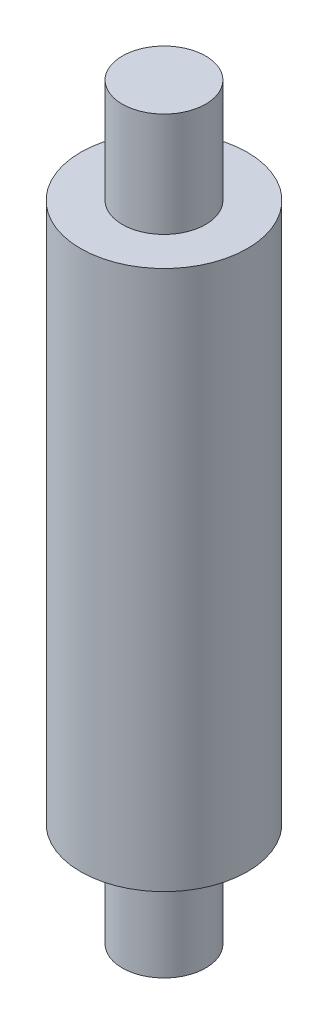
SolidWorks part; units mm, degrees
material "Plain Carbon Steel"
ref_plane "Front Plane" through (0, 0, 0) normal (0, 0, 1) x (1, 0, 0)
ref_plane "Top Plane" through (0, 0, 0) normal (0, 1, 0) x (1, 0, 0)
ref_plane "Right Plane" through (0, 0, 0) normal (1, 0, 0) x (0, 0, -1)
sketch "Sketch1" plane through (0, 0, 0) normal (0, 0, 1) x (1, 0, 0)
  line L0 (0, 30.988) -> (3.4544, 30.988)
  line L1 (3.4544, 30.988) -> (3.4544, 0)
  line L2 (3.4544, 0) -> (0, 0)
  line L3 (0, 0) -> (0, 30.988)
  line L4 (0, 0) -> (0, 30.988) construction
revolve "Revolve1" add sketch "Sketch1" angle 360 about L4 reverse direction yes
sketch "Sketch2" plane through (0, 0, 0) normal (0, 0, 1) x (1, 0, 0)
  line L0 (1.7272, 0) -> (3.4544, 0)
  line L1 (3.4544, 0) -> (3.4544, 4.318)
  line L2 (3.4544, 4.318) -> (1.7272, 4.318)
  line L3 (1.7272, 4.318) -> (1.7272, 0)
  line L4 (0, 0) -> (0, 4.318) construction
revolve "Cut-Revolve1" cut sketch "Sketch2" angle 360 about L4 reverse direction yes
sketch "Sketch3" plane through (0, 0, 0) normal (0, 0, 1) x (1, 0, 0)
  line L0 (1.7272, 30.988) -> (1.7272, 26.67)
  line L1 (1.7272, 26.67) -> (3.4544, 26.67)
  line L2 (3.4544, 26.67) -> (3.4544, 30.988)
  line L3 (3.4544, 30.988) -> (1.7272, 30.988)
  line L4 (0, 26.67) -> (0, 30.988) construction
revolve "Cut-Revolve2" cut sketch "Sketch3" angle 360 about L4 reverse direction yes
ref_plane "additional_rod XY" through (0, 0, 0) normal (0, 1, 0) x (1, 0, 0)
ref_plane "additional_rod XZ" through (0, 0, 0) normal (0, 0, 1) x (1, 0, 0)
ref_plane "additional_rod YZ" through (0, 0, 0) normal (1, 0, 0) x (0, 0, -1)
ref_axis "additional_rod X" through (-80.9, 0, 0) along (1, 0, 0)
ref_axis "additional_rod Y" through (0, 0, 50) along (0, 0, -1)
ref_axis "additional_rod Z" through (0, 50, 0) along (0, -1, 0)
sketch3d "additional_rod"
  point P0 (0, 0, 0)
